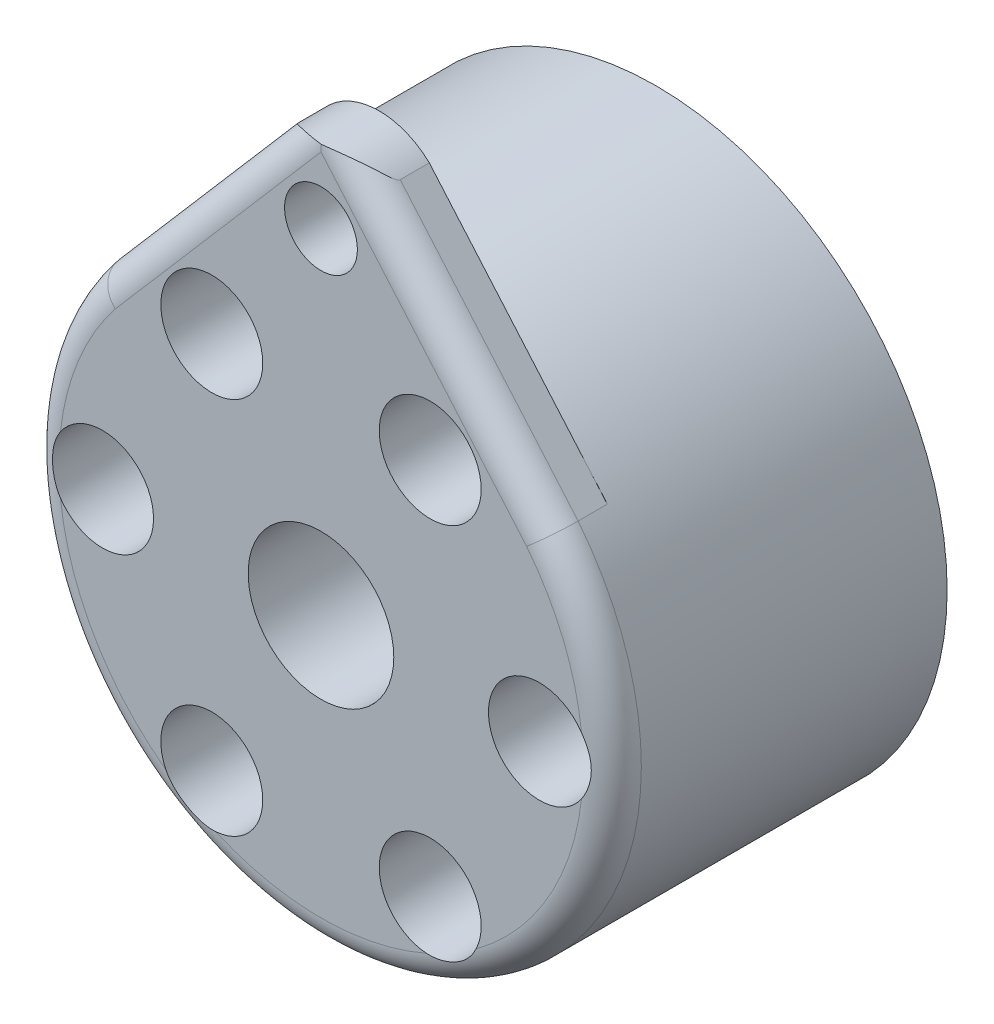
SolidWorks part; units mm, degrees
material "1060 合金"
ref_plane "前视基准面" through (0, 0, 0) normal (0, 0, 1) x (1, 0, 0)
ref_plane "上视基准面" through (0, 0, 0) normal (0, 1, 0) x (1, 0, 0)
ref_plane "右视基准面" through (0, 0, 0) normal (1, 0, 0) x (0, 0, -1)
sketch "草图1" plane through (0, 0, 0) normal (0, 0, 1) x (1, 0, 0)
  circle A0 centre (0, 0) radius 20
  circle A1 centre (-15, 0) radius 1.6
  circle A2 centre (-7.5, 12.9904) radius 1.6
  circle A3 centre (7.5, 12.9904) radius 1.6
  circle A4 centre (15, 0) radius 1.6
  circle A5 centre (7.5, -12.9904) radius 1.6
  circle A6 centre (-7.5, -12.9904) radius 1.6
  circle A7 centre (0, 0) radius 5
  point P16 (0, 0)
  dimension "D1" = 6
extrude "凸台-拉伸1" add sketch "草图1" along normal blind 19
sketch "Sketch1" plane through (0, 0, 19) normal (0, 0, 1) x (1, 0, 0)
  line L0 (-3.4388, 26.6297) -> (-15.6597, 12.4408)
  line L1 (3.4388, 26.6297) -> (15.6597, 12.4408)
  circle A0 centre (0, 0) radius 5
  circle A1 centre (0, 0) radius 20
  circle A2 centre (0, 0) radius 20
  circle A3 centre (-15, 0) radius 1.6
  circle A4 centre (-7.5, 12.9904) radius 1.6
  circle A5 centre (7.5, 12.9904) radius 1.6
  circle A6 centre (15, 0) radius 1.6
  circle A7 centre (7.5, -12.9904) radius 1.6
  circle A8 centre (-7.5, -12.9904) radius 1.6
  circle A9 centre (0, 23) radius 5
  circle A10 centre (0, 23) radius 2.5
  point P19 (0, 0)
  dimension "D2" = 6
  dimension "D1" = 0
extrude "Boss-Extrude1" add sketch "Sketch1" along normal blind 4
sketch "Sketch2" plane through (0, 0, 23) normal (0, 0, 1) x (1, 0, 0)
  circle A0 centre (-15, 0) radius 3.5
  circle A1 centre (-7.5, 12.9904) radius 3.5
  circle A2 centre (7.5, 12.9904) radius 3.5
  circle A3 centre (15, 0) radius 3.5
  circle A4 centre (7.5, -12.9904) radius 3.5
  circle A5 centre (-7.5, -12.9904) radius 3.5
  point P15 (0, 0)
  dimension "D1" = 6
extrude "Cut-Extrude1" cut sketch "Sketch2" against normal blind 5
fillet "Fillet2" radius 2 3 edges at (9.5493, 19.5352, 23) (-9.5493, 19.5352, 23) (0, -20, 23)
